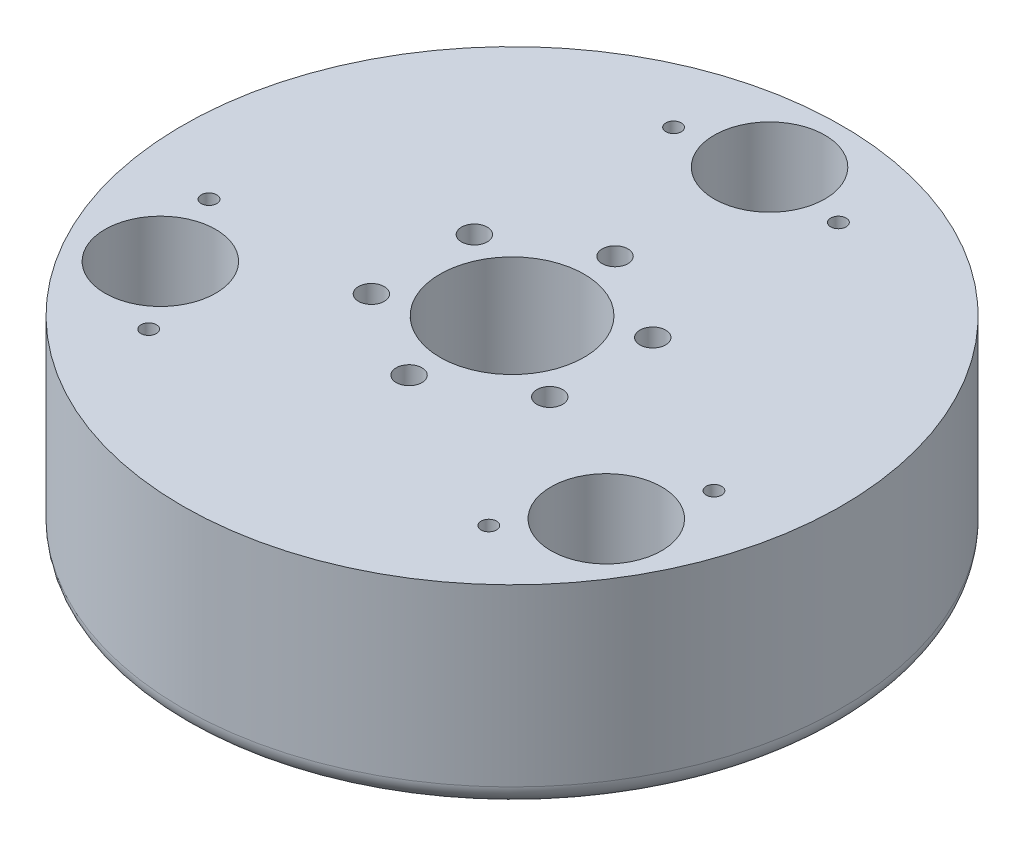
SolidWorks part; units mm, degrees
ref_plane "Спереди" through (0, 0, 0) normal (0, 0, 1) x (1, 0, 0)
ref_plane "Сверху" through (0, 0, 0) normal (0, 1, 0) x (1, 0, 0)
ref_plane "Справа" through (0, 0, 0) normal (1, 0, 0) x (0, 0, -1)
sketch "Эскиз1" plane through (0, 0, 0) normal (0, 1, 0) x (1, 0, 0)
  circle A3 centre (0, 0) radius 32
  circle A4 centre (0, 0) radius 4
  circle A6 centre (0, 0) radius 25 construction
  circle A7 centre (0, 25) radius 3
  circle A8 centre (21.6506, -12.5) radius 3
  circle A9 centre (-21.6506, -12.5) radius 3
  dimension "D4" = 64
  dimension "D1" = 8
  dimension "D2" = 50
  dimension "D3" = 6
  dimension "D5" = 3
extrude "Бобышка-Вытянуть1" add sketch "Эскиз1" along normal blind 19
fillet "Скругление1" radius 2 1 edges at (0, 0, 32)
sketch "Эскиз2" plane through (0, 19, 0) normal (0, 1, 0) x (1, 0, 0)
  circle A0 centre (0, 25) radius 5.375
  circle A2 centre (21.6506, -12.5) radius 5.375
  circle A3 centre (-21.6506, -12.5) radius 5.375
  circle A4 centre (-21.6506, -12.5) radius 3 construction
  dimension "D1" = 10.75
extrude "Вырез-Вытянуть1" cut sketch "Эскиз2" against normal blind 15.5
sketch "Эскиз3" plane through (0, 0, 0) normal (0, -1, 0) x (1, 0, 0)
  circle A0 centre (0, 0) radius 25 construction
  circle A1 centre (0, 25) radius 2.625
  circle A2 centre (21.6506, -12.5) radius 2.625
  circle A3 centre (-21.6506, -12.5) radius 2.625
  dimension "D1" = 5.25
extrude "Вырез-Вытянуть2" cut sketch "Эскиз3" against normal blind 15
sketch "Эскиз4" plane through (0, 19, 0) normal (0, 1, 0) x (1, 0, 0)
  circle A0 centre (0, 0) radius 10 construction
  circle A1 centre (0, 10) radius 1.25
  circle A2 centre (8.6603, 5) radius 1.25
  circle A3 centre (8.6603, -5) radius 1.25
  circle A4 centre (0, -10) radius 1.25
  circle A5 centre (-8.6603, -5) radius 1.25
  circle A6 centre (-8.6603, 5) radius 1.25
  dimension "D3" = 6
  dimension "D1" = 20
  dimension "D2" = 2.5
extrude "Вырез-Вытянуть3" cut sketch "Эскиз4" against normal through all
sketch "Эскиз7" plane through (0, 0, 0) normal (0, -1, 0) x (1, 0, 0)
  circle A0 centre (0, 10) radius 1.95 construction
  circle A7 centre (8.6603, 5) radius 1.95
  circle A8 centre (8.6603, -5) radius 1.95 construction
  circle A9 centre (0, -10) radius 1.95
  circle A10 centre (-8.6603, -5) radius 1.95 construction
  circle A11 centre (-8.6603, 5) radius 1.95
  circle A12 centre (8.6603, 5) radius 1.25 construction
  dimension "D1" = 3.9
  dimension "D2" = 6
extrude "Вырез-Вытянуть5" cut sketch "Эскиз7" against normal offset from surface (3 mm away) 16 up to face at (0, 19, -8.75)
chamfer "Фаска1" distance 1 angle 45 7 edges at (21.6506, 0, -15.125) (0, 0, -22) (-21.6506, 0, -15.125) (-21.6506, 0, 15.5) (0, 0, 22.375) (21.6506, 0, 15.5) (0, 0, 4)
sketch "Эскиз8" plane through (0, 19, 0) normal (0, 1, 0) x (1, 0, 0)
  circle A0 centre (0, 0) radius 7
  dimension "D1" = 14
extrude "Вырез-Вытянуть6" cut sketch "Эскиз8" against normal blind 10
sketch "Эскиз9" plane through (0, 19, 0) normal (0, 1, 0) x (1, 0, 0)
  line L0 (0, 0) -> (0, 25) construction
  line L1 (-8, 23.6854) -> (8, 23.6854) construction
  circle A0 centre (0, 0) radius 25 construction
  circle A1 centre (-8, 23.6854) radius 0.75
  circle A2 centre (8, 23.6854) radius 0.75
  circle A3 centre (16.5122, -18.7709) radius 0.75
  circle A4 centre (24.5122, -4.9145) radius 0.75
  circle A5 centre (-24.5122, -4.9145) radius 0.75
  circle A6 centre (-16.5122, -18.7709) radius 0.75
  dimension "D1" = 16
  dimension "D2" = 1.5
  dimension "D3" = 1.5
extrude "Вырез-Вытянуть7" cut sketch "Эскиз9" against normal through all
equation "\"motor_diameter\"= 30"
equation "\"mm_diameter\"= IIF ( \"motor_diameter\" < 34 , 41 , \"motor_diameter\" + 8 )"
equation "\"upper_shafts_diameter\"= 5"
equation "\"upper_shats_length\"= 180"
equation "\"upper_bearing_d1\"= 10"
equation "\"upper_bearing_d2\"= 5"
equation "\"upper_bearing_h\"= 15"
equation "\"lower_shafts_diameter\"= 5"
equation "\"lower_shafts_length\"= 180"
equation "\"lower_bearing_d1\"= 10"
equation "\"lower_bearing_d2\"= 5"
equation "\"lower_bearing_h\"= 15"
equation "\"print_offset\"= 0.5"
equation "\"bh_screws_d\"= 2"
equation "\"bh_screws_h\"= 20"
equation "\"bh_screws_hh_d\"= 3.4"
equation "\"bh_screws_hh_h\"= 2"
equation "\"bh_nut_d\"= 3.8"
equation "\"bh_nut_h\"= 2"
equation "\"motor_screws_d\"= 3"
equation "\"motor_screws_h\"= 16"
equation "\"motor_screws_hh_d\"= 5.5"
equation "\"motor_screws_hh_h\"= 3"
equation "\"plate_hole_distance\"= 25.4"
equation "\"plate_screws_d\"= 6.5"
equation "\"shafts_diameter\"= IIF ( \"mm_diameter\" < 42 , 42 + 8 , \"mm_diameter\" + 8 )"
equation "\"D4@Эскиз1\"= \"system_radius\" * 2"
equation "\"central_hole_diameter\"= 8"
equation "\"bh_thikness\"= 4"
equation "\"D1@Эскиз1\"=\"central_hole_diameter\""
equation "\"D2@Эскиз1\"=\"shafts_diameter\""
equation "\"D3@Эскиз1\" = \"lower_shafts_diameter\" + 1"
equation "\"D1@Бобышка-Вытянуть1\" = \"bh_thikness\" + \"lower_bearing_h\""
equation "\"D1@Эскиз2\" = \"lower_bearing_d1\" + \"print_offset\" * 1.5"
equation "\"D1@Вырез-Вытянуть1\" = \"lower_bearing_h\" + \"print_offset\""
equation "\"D1@Эскиз3\" = \"upper_shafts_diameter\" + \"print_offset\" / 2"
equation "\"D1@Вырез-Вытянуть2\"= \"upper_bearing_h\""
equation "\"D2@Эскиз4\"=\"bh_screws_d\"+\"print_offset\""
equation "\"D1@Вырез-Вытянуть5\"=\"bh_screws_h\"-\"bh_thikness\""
equation "\"D1@Эскиз7\"=\"bh_screws_hh_d\"+\"print_offset\""
equation "\"D1@Вырез-Вытянуть6\"=14-\"bh_thikness\""
equation "\"D2@Эскиз9\"=\"bh_screws_d\"-\"print_offset\""
equation "\"D3@Эскиз9\"=\"D2@Эскиз9\""
equation "\"ends_screws_d\"= 4"
equation "\"ends_screws_h\"= 16"
equation "\"ends_screws_hh_d\"= 6.7"
equation "\"ends_screws_hh_h\"= 4.1"
equation "\"ends_nut_d\"= 6.8"
equation "\"ends_nut_h\"= 3"
equation "\"system_radius\" = ( \"shafts_diameter\" + 12 + \"bh_thikness\" / 2 ) / 2"
equation "\"encoder_distance\"= \"system_radius\" + 4"
equation "\"tape_position\"= \"encoder_distance\" - 2 + 3.9 + 1.7 / 2"
